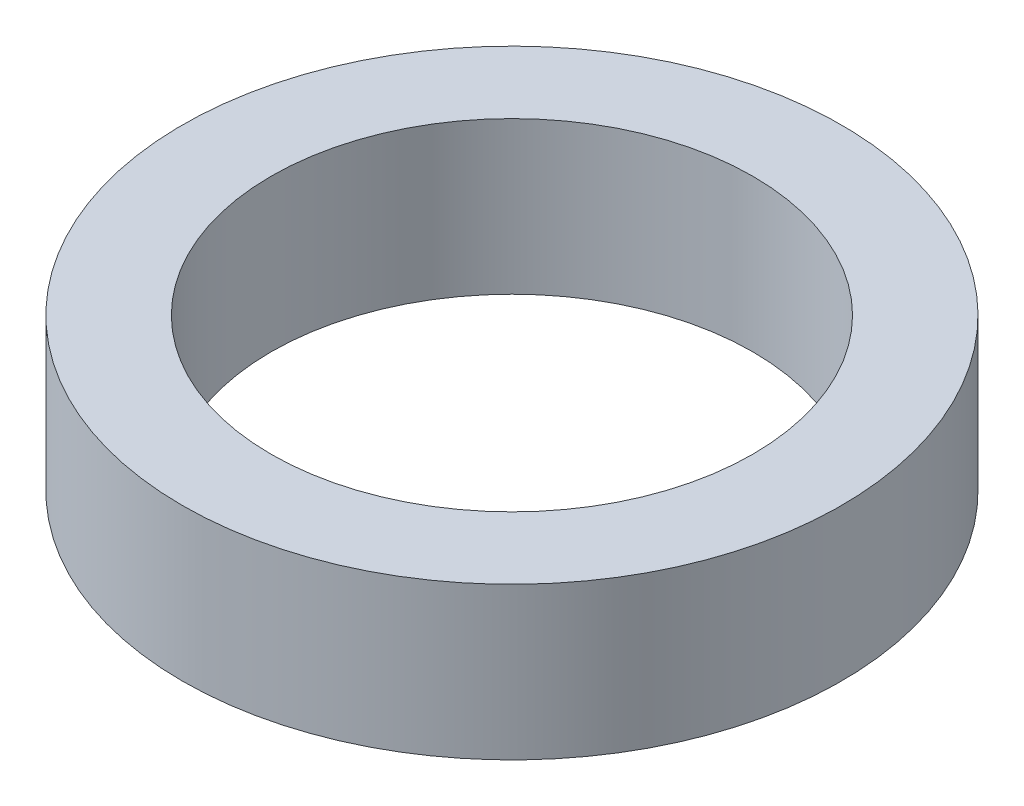
SolidWorks part; units mm, degrees
ref_plane "Front Plane" through (0, 0, 0) normal (0, 0, 1) x (1, 0, 0)
ref_plane "Top Plane" through (0, 0, 0) normal (0, 1, 0) x (1, 0, 0)
ref_plane "Right Plane" through (0, 0, 0) normal (1, 0, 0) x (0, 0, -1)
sketch "Sketch1" plane through (0, 0, 0) normal (0, 1, 0) x (1, 0, 0)
  circle A0 centre (0, 0) radius 65
  dimension "FLANGE_OD" = 130
extrude "Boss-Extrude1" add sketch "Sketch1" along normal blind 30
sketch "Sketch2" plane through (0, 0, 0) normal (0, 1, 0) x (1, 0, 0)
  circle A0 centre (0, 0) radius 47.5
  dimension "BORE_D" = 95
extrude "Cut-Extrude1" cut sketch "Sketch2" along normal through all
sketch "Sketch3" plane through (0, 30, 0) normal (0, 1, 0) x (1, 0, 0)
  circle A0 centre (0, 0) radius 28.9158 construction
  circle A1 centre (-28.9158, 0) radius 3.0087
  dimension "BOLT_D" = 6.0175
  dimension "BOLT_PCD" = 57.8315
extrude "Cut-Extrude2" cut sketch "Sketch3" against normal blind 23.0253 rebuild error yes
pattern_circular "CirPattern1" count 4 over 360 rebuild error yes
